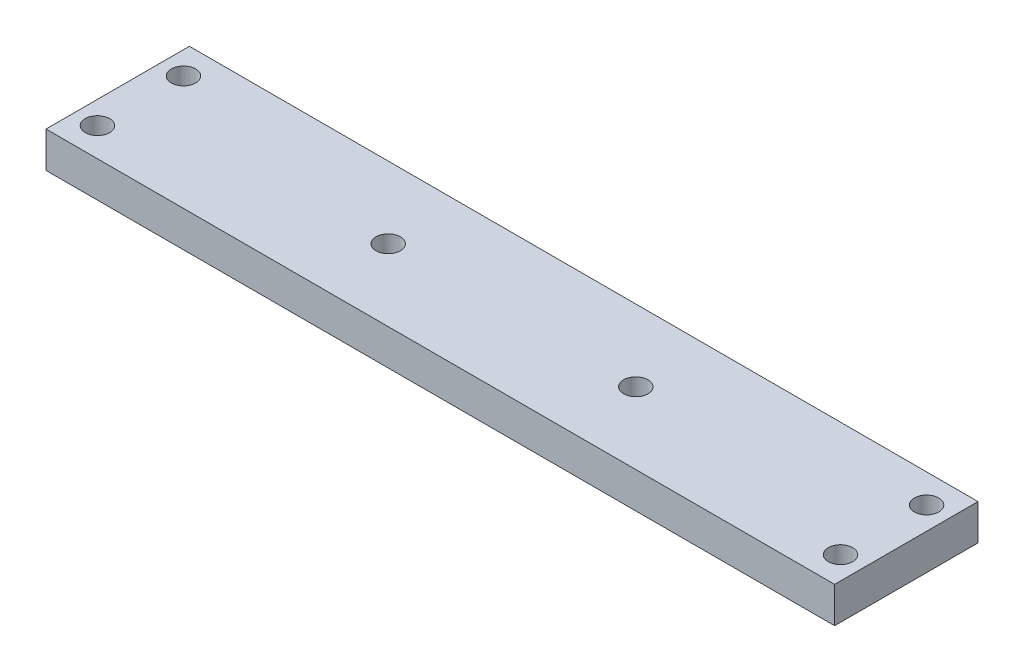
SolidWorks part; units mm, degrees
material "6061-T6 (SS)"
ref_plane "Front Plane" through (0, 0, 0) normal (0, 0, 1) x (1, 0, 0)
ref_plane "Top Plane" through (0, 0, 0) normal (0, 1, 0) x (1, 0, 0)
ref_plane "Right Plane" through (0, 0, 0) normal (1, 0, 0) x (0, 0, -1)
sketch "Sketch1" plane through (0, 0, 0) normal (0, 1, 0) x (1, 0, 0)
  line L5 (-55, -10) -> (55, -10)
  line L6 (-55, -10) -> (-55, 10)
  line L7 (-55, 10) -> (55, 10)
  line L8 (55, -10) -> (55, 10)
  line L9 (0, 10) -> (0, -10) construction
  line L10 (-55, 0) -> (55, 0) construction
  point P0 (0, 0)
  dimension "D1" = 20
  dimension "D2" = 110
extrude "Boss-Extrude1" add sketch "Sketch1" along normal mid plane 5
sketch "Sketch2" plane through (0, 2.5, 0) normal (0, 1, 0) x (1, 0, 0)
  line L0 (0, 10) -> (0, -10) construction
  line L1 (55, 10) -> (-55, 10) construction
  line L2 (-55, -10) -> (55, -10) construction
  line L3 (-55, 0) -> (55, 0) construction
  line L4 (-55, 10) -> (-55, -10) construction
  line L5 (55, -10) -> (55, 10) construction
  point P12 (-51.825, -6)
  point P14 (51.825, -6)
  point P16 (-51.825, 6)
  point P17 (51.825, 6)
  point P18 (17.275, 0)
  point P23 (-17.275, 0)
  dimension "D1" = 103.65
  dimension "D2" = 4
  dimension "D3" = 34.55
  dimension "D4" = 34.55
hole_wizard "M3 Clearance Hole1" positions "Sketch2" profile "Sketch3" hole size "M3" standard "ANSI Metric" end condition through all
sketch "Sketch3" plane through (-17.275, 2.5, 0) normal (1, 0, 0) x (0, 0, 1)
  line L0 (0, 0) -> (0, 5)
  line L1 (0, 5) -> (1.7, 5)
  line L2 (1.7, 5) -> (1.7, 0)
  line L5 (1.7, 0) -> (0, 0)
  line L11 (0, -6.35) -> (0, 107.95) construction
  dimension "Thru Hole Dia." = 3.4
  dimension "Thru Hole Depth" = 5
